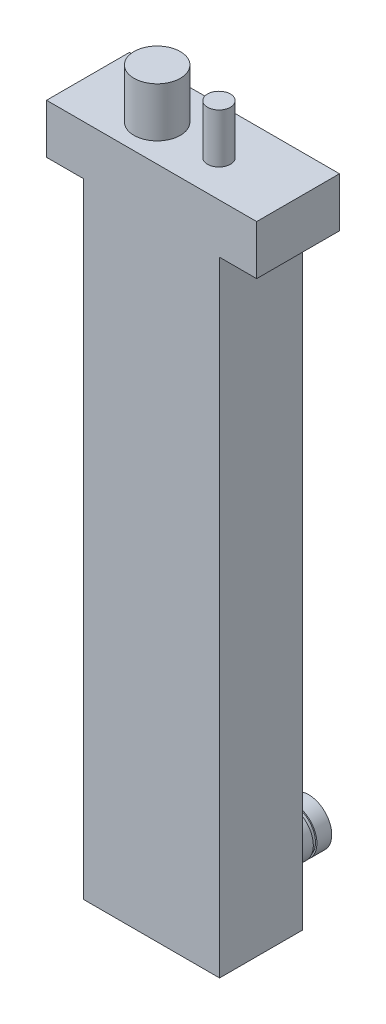
SolidWorks part; units mm, degrees
ref_plane "Front Plane" through (0, 0, 0) normal (0, 0, 1) x (1, 0, 0)
ref_plane "Top Plane" through (0, 0, 0) normal (0, 1, 0) x (1, 0, 0)
ref_plane "Right Plane" through (0, 0, 0) normal (1, 0, 0) x (0, 0, -1)
sketch "Sketch1" plane through (0, 0, 0) normal (0, 1, 0) x (1, 0, 0)
  line L1 (11.43, -9.525) -> (-21.59, -9.525)
  line L2 (11.43, -9.525) -> (11.43, 9.525)
  line L3 (11.43, 9.525) -> (-21.59, 9.525)
  line L4 (-21.59, -9.525) -> (-21.59, 9.525)
  point P0 (0, 0)
  dimension "D1" = 33.02
  dimension "D2" = 19.05
  dimension "D3" = 21.59
  dimension "D4" = 9.525
extrude "Boss-Extrude1" add sketch "Sketch1" along normal blind 10.16
sketch "Sketch2" plane through (0, 10.16, 0) normal (0, 1, 0) x (1, 0, 0)
  line L0 (-21.59, 9.525) -> (-21.59, -9.525) construction
  circle A0 centre (-11.43, 0) radius 4.7625
  circle A1 centre (1.27, 0) radius 2.3573
  point P6 (0, 0)
  point P7 (-21.59, 0)
  point P8 (0, 0)
  dimension "D1" = 10.16
  dimension "D3" = 9.525
  dimension "D4" = 4.7146
  dimension "D2" = 22.86
extrude "Boss-Extrude2" add sketch "Sketch2" along normal blind 10.16
sketch "Sketch5" plane through (-21.59, 0, 0) normal (-1, 0, 0) x (0, 0, 1)
  line L1 (-9.525, 0) -> (9.525, 0)
  line L2 (-9.525, 0) -> (-9.525, 10.16)
  line L3 (-9.525, 10.16) -> (9.525, 10.16)
  line L4 (9.525, 0) -> (9.525, 10.16)
extrude "Boss-Extrude3" add sketch "Sketch5" along normal blind 5.08
sketch "Sketch6" plane through (11.43, 0, 0) normal (1, 0, 0) x (0, 0, -1)
  line L1 (-9.525, 10.16) -> (9.525, 10.16)
  line L2 (-9.525, 10.16) -> (-9.525, 0)
  line L3 (-9.525, 0) -> (9.525, 0)
  line L4 (9.525, 10.16) -> (9.525, 0)
extrude "Boss-Extrude4" add sketch "Sketch6" along normal blind 5.08
sketch "Sketch7" plane through (0, 0, 0) normal (0, -1, 0) x (-1, 0, 0)
  line L0 (26.67, -9.525) -> (-16.51, -9.525) construction
  line L1 (19.05, -9.525) -> (-8.89, -9.525)
  line L2 (19.05, -9.525) -> (19.05, 9.525)
  line L3 (19.05, 9.525) -> (-8.89, 9.525)
  line L4 (-8.89, -9.525) -> (-8.89, 9.525)
  line L5 (-16.51, 9.525) -> (26.67, 9.525) construction
  line L6 (-16.51, -9.525) -> (-16.51, 9.525) construction
  line L7 (26.67, 9.525) -> (26.67, -9.525) construction
  point P10 (-16.51, 0)
  dimension "D1" = 7.62
  dimension "D2" = 7.62
extrude "Boss-Extrude5" add sketch "Sketch7" along normal blind 128.27
sketch "Sketch9" plane through (0, 0, 9.525) normal (0, 0, 1) x (1, 0, 0)
  line L0 (8.89, -128.27) -> (-19.05, -128.27) construction
  line L1 (-19.05, -128.27) -> (-19.05, 0) construction
  circle A0 centre (-5.08, -123.5075) radius 4.7625
  point P4 (0, 0)
  point P5 (-5.08, -122.9819)
  dimension "D1" = 9.525
  dimension "D2" = 4.7625
  dimension "D3" = 13.97
extrude "Boss-Extrude6" add sketch "Sketch9" along normal blind 15.24
mirror "Mirror5" about plane through (0, 0, 0) normal (0, 0, 1) of "Boss-Extrude6"
sketch3d "3DSketch2"
  circle A0 centre (-5.08, -123.5075, -21.717) radius 5.08
  circle A1 centre (-5.08, -123.5075, -24.765) radius 4.7625 construction
  point P2 (-5.08, -123.5075, -26.797)
  point P5 (-5.08, -123.5075, -20.0025)
  point P7 (0, 0, 0)
  dimension "D2" = 10.16
  dimension "D1" = 3.048
extrude "Cut-Extrude3" cut sketch "3DSketch2" along direction (0, 0, -1) on the side against the normal blind 0.7366
sketch "Sketch13" plane through (0, 0, -20.9804) normal (0, 0, -1) x (-1, 0, 0)
  circle A0 centre (5.08, -123.5075) radius 4.4704
  dimension "D1" = 8.9408
extrude "Boss-Extrude8" add sketch "Sketch13" along normal up to surface (0.7366 mm away) up to face at (-0.3175, -123.5075, -21.717)
sketch "Sketch14" plane through (0, 0, 9.525) normal (0, 0, 1) x (1, 0, 0)
  line L0 (-19.05, -128.27) -> (-19.05, 0) construction
  line L1 (-19.05, -118.11) -> (8.89, -118.11)
  line L2 (-19.05, -118.11) -> (-19.05, -128.27)
  line L3 (-19.05, -128.27) -> (8.89, -128.27)
  line L4 (8.89, -118.11) -> (8.89, -128.27)
  dimension "D1" = 10.16
extrude "Cut-Extrude4" cut sketch "Sketch14" along normal up to surface (15.24 mm away) up to face at (-0.3175, -123.5075, 24.765)
sketch "Sketch15" plane through (0, 0, 9.525) normal (0, 0, 1) x (1, 0, 0)
  line L0 (8.89, -128.27) -> (-19.05, -128.27) construction
  line L1 (-26.67, 10.16) -> (16.51, 10.16)
  line L2 (-26.67, 10.16) -> (-26.67, -128.27)
  line L3 (-26.67, -128.27) -> (16.51, -128.27)
  line L4 (16.51, 10.16) -> (16.51, -128.27)
  line L5 (16.51, 10.16) -> (16.51, 0) construction
extrude "Cut-Extrude5" cut sketch "Sketch15" against normal blind 2.032
